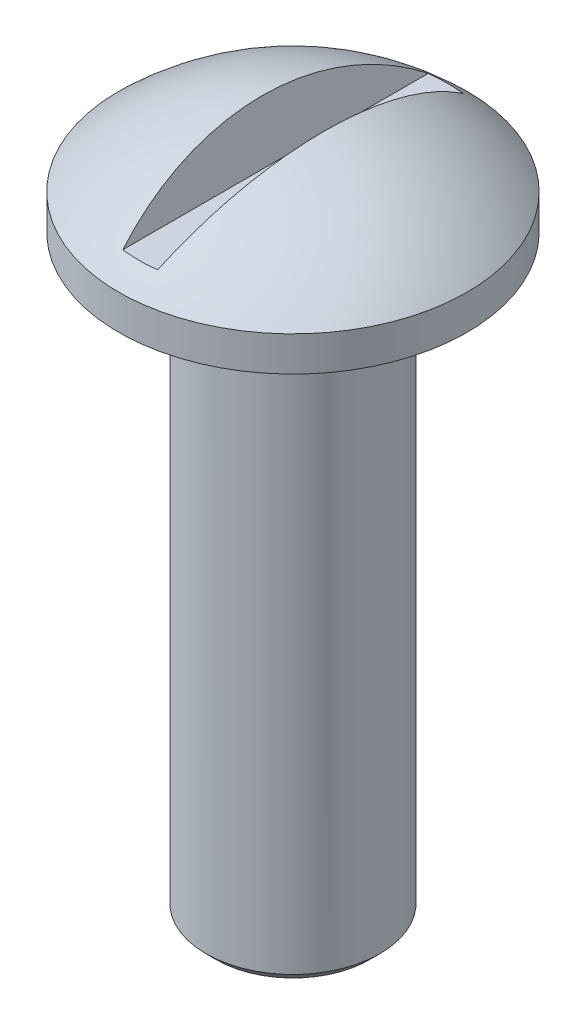
SolidWorks part; units mm, degrees
ref_plane "Front Plane" through (0, 0, 0) normal (0, 0, 1) x (1, 0, 0)
ref_plane "Top Plane" through (0, 0, 0) normal (0, 1, 0) x (1, 0, 0)
ref_plane "Right Plane" through (0, 0, 0) normal (1, 0, 0) x (0, 0, -1)
sketch "Sketch1" plane through (0, 0, 0) normal (0, 0, 1) x (1, 0, 0)
  line L0 (0, 0) -> (0, 67.3355) construction
  line L1 (0, 0) -> (0, 45.72)
  line L2 (0, 45.72) -> (-12.7, 45.72)
  line L3 (-12.7, 45.72) -> (-12.7, 43.18)
  line L4 (-12.7, 43.18) -> (-6.35, 43.18)
  line L5 (-6.35, 43.18) -> (-6.35, 0)
  line L6 (-6.35, 0) -> (0, 0)
  dimension "D1" = 2.54
  dimension "D2" = 43.18
  dimension "D3" = 12.7
  dimension "D4" = 25.4
revolve "Revolve1" add sketch "Sketch1" angle 360 about L0
dome "Dome2" faces to dome 1 distance 5.08 reverse direction no elliptical dome no face at (0, 45.72, -12.7) parameters "D1"=5.08
sketch "Sketch2" plane through (0, 0, 0) normal (0, 0, 1) x (1, 0, 0)
  line L0 (0, 0) -> (0, 60.824) construction
  line L1 (1.27, 46.99) -> (-1.27, 46.99)
  line L2 (-1.27, 46.99) -> (-3.2622, 54.425)
  line L3 (-3.2622, 54.425) -> (3.2622, 54.425)
  line L4 (1.27, 46.99) -> (3.2622, 54.425)
  line L5 (-6.35, 43.18) -> (6.35, 43.18) construction
  point P8 (0, 46.99)
  point P9 (0, 54.425)
  dimension "D1" = 3.81
  dimension "D2" = 2.54
  dimension "D3" = 30
extrude "Cut-Extrude2" cut sketch "Sketch2" against normal through all both and the other way through all
chamfer "Chamfer1" distance 0.762 angle 45 1 edges at (0, 0, -6.35)
